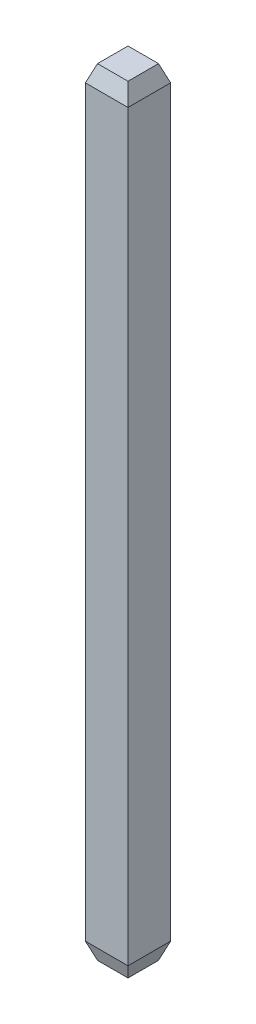
SolidWorks part; units mm, degrees
ref_plane "Спереди" through (0, 0, 0) normal (0, 0, 1) x (1, 0, 0)
ref_plane "Сверху" through (0, 0, 0) normal (0, 1, 0) x (1, 0, 0)
ref_plane "Справа" through (0, 0, 0) normal (1, 0, 0) x (0, 0, -1)
other "Configuration Table"
sketch "Эскиз1" plane through (0, 0, 0) normal (0, 1, 0) x (1, 0, 0)
  line L1 (-0.32, -0.32) -> (0.32, -0.32)
  line L2 (-0.32, -0.32) -> (-0.32, 0.32)
  line L3 (-0.32, 0.32) -> (0.32, 0.32)
  line L4 (0.32, -0.32) -> (0.32, 0.32)
  line L5 (0, 0.32) -> (0, -0.32) construction
  line L6 (-0.32, 0) -> (0.32, 0) construction
  point P0 (0, 0)
  dimension "D1" = 0.64
extrude "Бобышка-Вытянуть1" add sketch "Эскиз1" along normal blind 11.66
sketch "Эскиз2" plane through (0, 11.66, 0) normal (0, 1, 0) x (1, 0, 0)
  line L1 (0.32, 0.32) -> (-0.32, 0.32)
  line L2 (0.32, 0.32) -> (0.32, -0.32)
  line L3 (0.32, -0.32) -> (-0.32, -0.32)
  line L4 (-0.32, 0.32) -> (-0.32, -0.32)
  line L5 (0, -0.32) -> (0, 0.32) construction
  line L6 (0.32, 0) -> (-0.32, 0) construction
  point P0 (0, 0)
chamfer "Фаска1" distance 0.25 angle 20 4 edges at (0.32, 11.66, 0) (0, 11.66, 0.32) (-0.32, 11.66, 0) (0, 11.66, -0.32) first distance on face at (0.32, 5.83, 0) first distance on face at (0, 5.83, 0.32) first distance on face at (-0.32, 5.83, 0) first distance on face at (0, 5.83, -0.32)
chamfer "Фаска2" distance 0.25 angle 20 4 edges at (0, 0, -0.32) (-0.32, 0, 0) (0, 0, 0.32) (0.32, 0, 0) first distance on face at (0, 5.705, -0.32) first distance on face at (-0.32, 5.705, 0) first distance on face at (0, 5.705, 0.32) first distance on face at (0.32, 5.705, 0)
